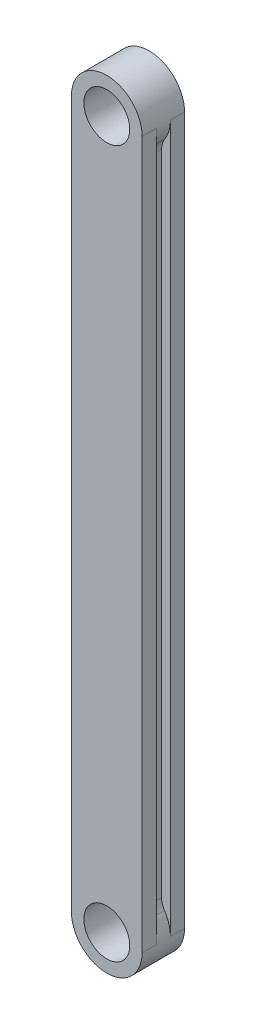
SolidWorks part; units mm, degrees
ref_plane "Front Plane" through (0, 0, 0) normal (0, 0, 1) x (1, 0, 0)
ref_plane "Top Plane" through (0, 0, 0) normal (0, 1, 0) x (1, 0, 0)
ref_plane "Right Plane" through (0, 0, 0) normal (1, 0, 0) x (0, 0, -1)
sketch "Sketch1" plane through (0, 0, 0) normal (0, 1, 0) x (1, 0, 0)
  line L0 (0, 37.3121) -> (0, -37.0351) construction
  line L1 (-20, 12) -> (20, 12)
  line L2 (-20, 12) -> (-20, 4)
  line L3 (-20, -12) -> (20, -12)
  line L4 (20, 12) -> (20, 4)
  line L5 (-20, 12) -> (20, -12) construction
  line L6 (-20, -12) -> (20, 12) construction
  line L7 (-20, 4) -> (-15, 4)
  line L9 (-20, -4) -> (-15, -4)
  line L10 (15, 4) -> (15, -4)
  line L11 (-20, 4) -> (-20, 5.6964) construction
  line L12 (20, 4) -> (20, -4) construction
  line L13 (20, -4) -> (15, -4)
  line L15 (-23.3736, 0) -> (27.6022, 0) construction
  line L16 (-15, 4) -> (-15, -4)
  line L17 (20, 4) -> (15, 4)
  line L18 (-20, -4) -> (-20, -12)
  line L20 (20, -4) -> (20, -12)
  point P0 (0, 0)
  point P6 (-45, 0)
  point P22 (-15, 0)
  dimension "D1" = 40
  dimension "D2" = 24
  dimension "D3" = 8
  dimension "D4" = 5
extrude "Boss-Extrude1" add sketch "Sketch1" along normal blind 400
sketch "Sketch2" plane through (0, 0, -12) normal (0, 0, -1) x (-1, 0, 0)
  line L0 (-20, 0) -> (20, 0) construction
  line L1 (20, 400) -> (20, 0) construction
  circle A0 centre (0, 0) radius 20
extrude "Boss-Extrude2" add sketch "Sketch2" against normal up to surface (24 mm away) up to face at (0, 200, 12)
ref_plane "Plane1" through (0, 200, 0) normal (0, 1, 0) x (1, 0, 0)
mirror "Mirror1" about plane through (0, 200, 0) normal (0, 1, 0) of "Boss-Extrude2"
fillet "Fillet1" radius 10 4 edges at (-15, 386.7712, 0) (15, 386.7712, 0) (15, 13.2288, 0) (-15, 13.2288, 0)
sketch "Sketch3" plane through (0, 0, -12) normal (0, 0, -1) x (-1, 0, 0)
  circle A0 centre (0, 400) radius 13
  dimension "D1" = 26
extrude "Cut-Extrude1" cut sketch "Sketch3" against normal up to next contours A0
mirror "Mirror2" about plane through (0, 200, 0) normal (0, 1, 0) of "Cut-Extrude1"
